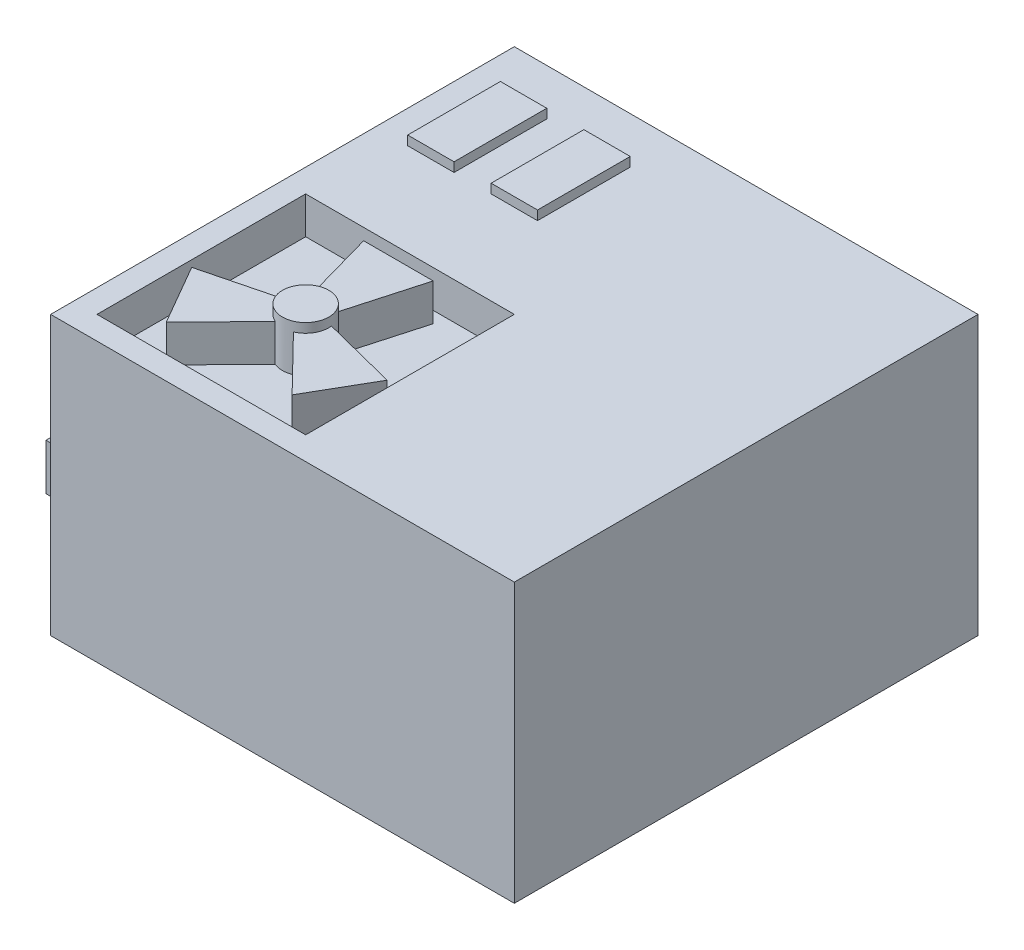
SolidWorks part; units mm, degrees
ref_plane "前视基准面" through (0, 0, 0) normal (0, 0, 1) x (1, 0, 0)
ref_plane "上视基准面" through (0, 0, 0) normal (0, 1, 0) x (1, 0, 0)
ref_plane "右视基准面" through (0, 0, 0) normal (1, 0, 0) x (0, 0, -1)
sketch "草图1" plane through (0, 0, 0) normal (0, 1, 0) x (1, 0, 0)
  line L1 (-50, -50) -> (50, -50)
  line L2 (-50, -50) -> (-50, 50)
  line L3 (-50, 50) -> (50, 50)
  line L4 (50, -50) -> (50, 50)
  line L5 (0, 50) -> (0, -50) construction
  line L6 (-50, 0) -> (50, 0) construction
  point P0 (0, 0)
  dimension "D1" = 100
  dimension "D2" = 100
extrude "凸台-拉伸1" add sketch "草图1" along normal blind 60
sketch "草图2" plane through (0, 60, 0) normal (0, 1, 0) x (1, 0, 0)
  line L0 (-50, 50) -> (-50, -50) construction
  line L1 (-45, 0) -> (0, 0)
  line L2 (-45, 0) -> (-45, -45)
  line L3 (-45, -45) -> (0, -45)
  line L4 (0, 0) -> (0, -45)
  line L5 (-50, -50) -> (50, -50) construction
  dimension "D1" = 45
  dimension "D2" = 45
  dimension "D3" = 5
  dimension "D4" = 5
extrude "切除-拉伸1" cut sketch "草图2" against normal blind 8
sketch "草图3" plane through (0, 60, 0) normal (0, 1, 0) x (1, 0, 0)
  line L0 (-50, 50) -> (-50, -50) construction
  line L1 (-43, 40) -> (-33, 40)
  line L2 (-43, 40) -> (-43, 20)
  line L3 (-43, 20) -> (-33, 20)
  line L4 (-33, 40) -> (-33, 20)
  line L5 (-25, 40) -> (-15, 40)
  line L6 (-25, 40) -> (-25, 20)
  line L7 (-25, 20) -> (-15, 20)
  line L8 (-15, 40) -> (-15, 20)
  line L9 (50, 50) -> (-50, 50) construction
  dimension "D1" = 20
  dimension "D2" = 10
  dimension "D3" = 10
  dimension "D4" = 20
  dimension "D5" = 8
  dimension "D6" = 7
  dimension "D7" = 10
extrude "凸台-拉伸2" add sketch "草图3" along normal blind 2
sketch "草图4" plane through (-50, 0, 0) normal (-1, 0, 0) x (0, 0, 1)
  line L0 (-50, 0) -> (50, 0) construction
  line L1 (5, 30) -> (25, 30)
  line L2 (5, 30) -> (5, 20)
  line L3 (5, 20) -> (25, 20)
  line L4 (25, 30) -> (25, 20)
  line L5 (50, 60) -> (50, 0) construction
  line L7 (39, 35) -> (49, 35)
  line L8 (39, 35) -> (39, 25)
  line L9 (39, 25) -> (49, 25)
  line L10 (49, 35) -> (49, 25)
  dimension "D1" = 10
  dimension "D2" = 20
  dimension "D3" = 20
  dimension "D4" = 25
  dimension "D5" = 10
  dimension "D6" = 10
  dimension "D7" = 1
  dimension "D8" = 25
extrude "凸台-拉伸3" add sketch "草图4" along normal blind 2
sketch "草图5" plane through (-50, 0, 0) normal (-1, 0, 0) x (0, 0, 1)
  line L1 (-50, 60) -> (50, 60) construction
  line L3 (50, 60) -> (50, 0) construction
  circle A0 centre (15, 47) radius 2.5
  circle A1 centre (15, 47) radius 5
  circle A2 centre (35, 47) radius 5
  circle A3 centre (35, 47) radius 2.5
  dimension "D1" = 10
  dimension "D2" = 5
  dimension "D3" = 5
  dimension "D4" = 10
  dimension "D5" = 8
  dimension "D6" = 10
  dimension "D7" = 10
extrude "凸台-拉伸4" add sketch "草图5" along normal blind 2
fillet "圆角1" 2 edges at (-52, 47, 20) (-52, 47, 17.5) type full round first side face at (-52, 47, 20) second side face at (-52, 47, 17.5) middle face at (-52, 47, 20)
fillet "圆角2" 2 edges at (-52, 47, 37.5) (-52, 47, 40) type full round first side face at (-52, 47, 37.5) second side face at (-52, 47, 40) middle face at (-52, 47, 40)
sketch "草图6" plane through (0, 52, 0) normal (0, 1, 0) x (1, 0, 0)
  line L0 (-25.5, -18.5) -> (-30, -2.5)
  line L1 (-30, -2.5) -> (-15, -2.5)
  line L2 (-15, -2.5) -> (-19.5, -18.5)
  line L3 (-22.5, -22.5) -> (-22.5, 0) construction
  line L4 (0, 0) -> (-45, 0) construction
  line L5 (-45, -22.5) -> (-22.5, -22.5) construction
  line L6 (-45, 0) -> (-45, -45) construction
  line L7 (-17.5359, -21.9019) -> (-1.4295, -26.0048)
  line L8 (-1.4295, -26.0048) -> (-8.9295, -38.9952)
  line L9 (-8.9295, -38.9952) -> (-20.5359, -27.0981)
  line L10 (-24.4641, -27.0981) -> (-36.0705, -38.9952)
  line L11 (-36.0705, -38.9952) -> (-43.5705, -26.0048)
  line L12 (-43.5705, -26.0048) -> (-27.4641, -21.9019)
  arc A0 (-24.4641, -27.0981) -> (-20.5359, -27.0981) centre (-22.5, -22.5) ccw
  arc A1 (-17.5359, -21.9019) -> (-19.5, -18.5) centre (-22.5, -22.5) ccw
  arc A2 (-25.5, -18.5) -> (-27.4641, -21.9019) centre (-22.5, -22.5) ccw
  dimension "D1" = 10
  dimension "D2" = 15
  dimension "D3" = 6
  dimension "D4" = 15
  dimension "D5" = 3
extrude "凸台-拉伸5" add sketch "草图6" along normal up to surface (8 mm away) up to face at (-20, 60, -30)
sketch "草图7" plane through (0, 60, 0) normal (0, 1, 0) x (1, 0, 0)
  circle A0 centre (-22.5, -22.5) radius 5
extrude "凸台-拉伸6" add sketch "草图7" along normal blind 2
